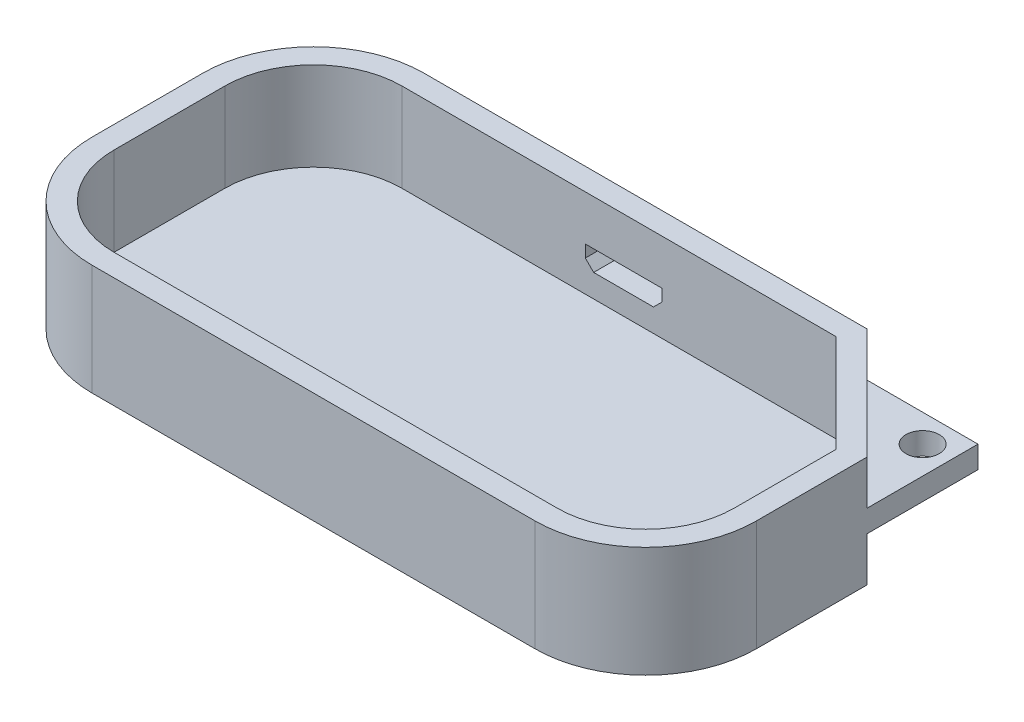
SolidWorks part; units mm, degrees
ref_plane "Front Plane" through (0, 0, 0) normal (0, 0, 1) x (1, 0, 0)
ref_plane "Top Plane" through (0, 0, 0) normal (0, 1, 0) x (1, 0, 0)
ref_plane "Right Plane" through (0, 0, 0) normal (1, 0, 0) x (0, 0, -1)
sketch "Sketch1" plane through (0, 0, 0) normal (0, 1, 0) x (1, 0, 0)
  line L0 (-32.5827, 22.5928) -> (27.4173, 22.5928)
  line L1 (27.4173, 22.5928) -> (27.4173, -7.4072)
  line L2 (-32.5827, 22.5928) -> (-32.5827, -7.4072)
  line L3 (-32.5827, -7.4072) -> (27.4173, -7.4072)
extrude "Boss-Extrude1" add sketch "Sketch1" along normal blind 10
fillet "Fillet1" radius 10 1 edges at (27.4173, 5, 7.4072)
fillet "Fillet3" radius 10 1 edges at (-32.5827, 5, 7.4072)
fillet "Fillet4" radius 10 1 edges at (-32.5827, 5, -22.5928)
sketch "Sketch6" plane through (0, 10, 0) normal (0, 1, 0) x (1, 0, 0)
  line L0 (27.4173, 12.5928) -> (17.4173, 22.5928) construction
  line L1 (27.4173, 2.5928) -> (27.4173, 22.5928) construction
  line L2 (27.4173, 22.5928) -> (-22.5827, 22.5928) construction
  line M1 (27.4173, 22.5928) -> (-22.5827, 22.5928)
  line M7 (27.4173, 2.5928) -> (27.4173, 22.5928)
extrude "Cut-Extrude1" cut sketch "Sketch6" against normal blind 4 contours L0 M7 M1 region at (24.0839, 10, -19.2594)
sketch "Sketch7" plane through (0, 0, 0) normal (0, -1, 0) x (1, 0, 0)
  line L0 (27.4173, -12.5928) -> (17.4173, -22.5928) construction
  line M3 (-22.5827, -22.5928) -> (27.4173, -22.5928)
  line M4 (27.4173, -22.5928) -> (27.4173, -2.5928)
extrude "Cut-Extrude2" cut sketch "Sketch7" against normal blind 4 contours L0 M4 M3 region at (24.0839, 0, -19.2594)
sketch "Sketch8" plane through (0, 6, 0) normal (0, 1, 0) x (1, 0, 0)
  line L0 (27.4173, 17.5928) -> (18.7686, 17.5928) construction
  line L1 (27.4173, 12.5928) -> (27.4173, 22.5928) construction
  line L2 (22.4173, 22.5928) -> (22.4173, 15.2043) construction
  line L3 (27.4173, 22.5928) -> (17.4173, 22.5928) construction
  line L4 (27.4173, 22.5928) -> (22.4173, 17.5928) construction
  line L5 (27.4173, 12.5928) -> (17.4173, 22.5928) construction
  circle A0 centre (24.9173, 20.0928) radius 1.5
extrude "Cut-Extrude3" cut sketch "Sketch8" against normal blind 4
shell "Shell5" thickness 2 removed face at (-2.8416, 10, -7.3339)
sketch "Sketch10" plane through (0, 0, -22.5928) normal (0, 0, -1) x (-1, 0, 0)
  line L0 (-17.4173, 6) -> (-17.4173, 4) construction
  line L7 (2.5827, 5.925) -> (6.0327, 5.925)
  line L11 (2.5827, 5.925) -> (-0.8673, 5.925)
  line L12 (-0.8673, 5.925) -> (-0.8673, 4.825)
  line L13 (6.0327, 5.925) -> (6.0327, 4.825)
  line L14 (2.5827, 4.075) -> (5.2827, 4.075)
  line L15 (2.5827, 4.075) -> (-0.1173, 4.075)
  line L16 (-0.8673, 4.825) -> (-0.1173, 4.075)
  line L17 (5.2827, 4.075) -> (6.0327, 4.825)
  point P9 (0, 0)
extrude "Cut-Extrude4" cut sketch "Sketch10" against normal blind 2
sketch "Sketch11" plane through (0, 0, -22.5928) normal (0, 0, -1) x (-1, 0, 0)
  line L0 (2.5827, 10) -> (2.5827, 0) construction
  line L1 (-17.4173, 10) -> (22.5827, 10) construction
  line L2 (-17.4173, 0) -> (22.5827, 0) construction
  line L3 (2.5827, 5) -> (22.5827, 5) construction
  line L4 (22.5827, 0) -> (22.5827, 10) construction
  line L5 (12.5827, 5) -> (12.5827, 10) construction
  line L6 (12.5827, 5) -> (12.5827, 0) construction
  line L8 (9.1513, 3.25) -> (16.0142, 3.25)
  line L9 (9.1513, 3.25) -> (9.1513, 6.75)
  line L10 (9.1513, 6.75) -> (16.0142, 6.75)
  line L11 (16.0142, 3.25) -> (16.0142, 6.75)
  line L12 (12.5827, 6.75) -> (12.5827, 3.25) construction
  line L13 (9.1513, 5) -> (16.0142, 5) construction
extrude "Boss-Extrude2" add sketch "Sketch11" along normal blind 1
sketch "Sketch12" plane through (0, 0, -23.5928) normal (0, 0, -1) x (-1, 0, 0)
  line L0 (12.5827, 6.75) -> (12.5827, 5) construction
  line L1 (12.5827, 5) -> (12.7358, 5)
  line L2 (12.5827, 5) -> (12.4287, 5)
  line L3 (16.0142, 6.75) -> (9.1513, 6.75) construction
  line L4 (12.4287, 5) -> (12.4287, 6.2971)
  line L5 (12.4287, 6.2971) -> (12.7358, 6.2971)
  line L6 (12.1115, 5.8829) -> (12.2041, 5.7095)
  line L7 (13.054, 5.8829) -> (12.9614, 5.7095)
  line L8 (12.7358, 6.2971) -> (12.7358, 5)
  arc A0 (12.1115, 5.8829) -> (13.054, 5.8829) centre (12.5827, 5) ccw
  arc A1 (12.2041, 5.7095) -> (12.9614, 5.7095) centre (12.5827, 5) ccw
extrude "Cut-Extrude5" cut sketch "Sketch12" against normal blind 0.1
ref_plane "Plane1" through (27.4173, 4, -22.5928) normal (0, -1, 0) x (-1, 0, 0)
